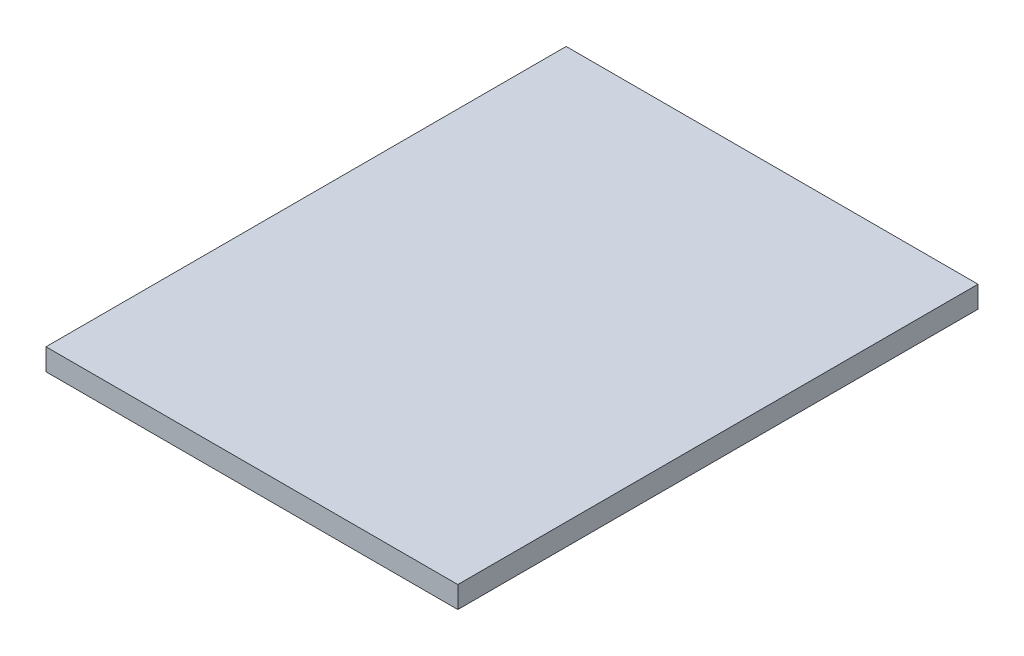
SolidWorks part; units mm, degrees
ref_plane "Front Plane" through (0, 0, 0) normal (0, 0, 1) x (1, 0, 0)
ref_plane "Top Plane" through (0, 0, 0) normal (0, 1, 0) x (1, 0, 0)
ref_plane "Right Plane" through (0, 0, 0) normal (1, 0, 0) x (0, 0, -1)
sketch "Sketch2" plane through (0, 0, 0) normal (0, 1, 0) x (1, 0, 0)
  line L1 (-47.5, -60) -> (47.5, -60)
  line L2 (-47.5, -60) -> (-47.5, 60)
  line L3 (-47.5, 60) -> (47.5, 60)
  line L4 (47.5, -60) -> (47.5, 60)
  line L5 (-47.5, -60) -> (47.5, 60) construction
  line L6 (-47.5, 60) -> (47.5, -60) construction
  point P0 (0, 0)
  dimension "D1" = 120
  dimension "D2" = 95
extrude "Boss-Extrude1" add sketch "Sketch2" along normal blind 5
